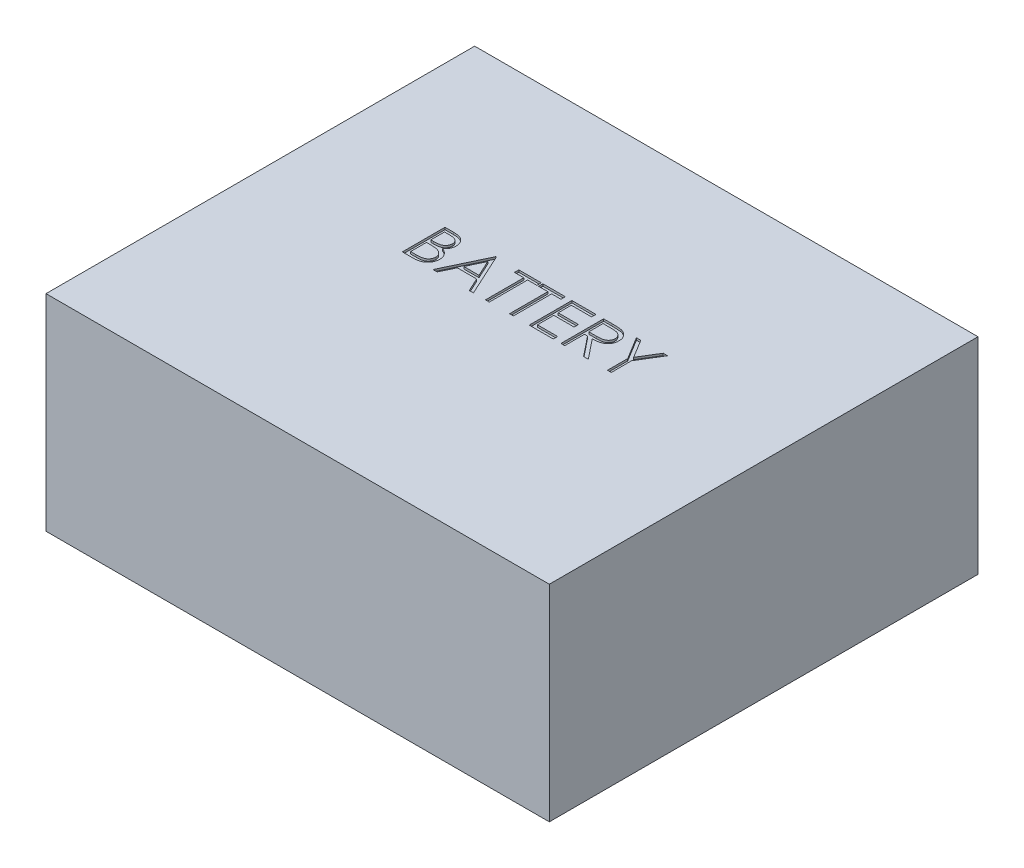
SolidWorks part; units mm, degrees
ref_plane "Front Plane" through (0, 0, 0) normal (0, 0, 1) x (1, 0, 0)
ref_plane "Top Plane" through (0, 0, 0) normal (0, 1, 0) x (1, 0, 0)
ref_plane "Right Plane" through (0, 0, 0) normal (1, 0, 0) x (0, 0, -1)
sketch "Sketch1" plane through (0, 0, 0) normal (0, 1, 0) x (1, 0, 0)
  line L1 (0, 0) -> (236, 0)
  line L2 (0, 0) -> (0, 201)
  line L3 (0, 201) -> (236, 201)
  line L4 (236, 0) -> (236, 201)
  dimension "D1" = 201
  dimension "D2" = 236
extrude "Boss-Extrude1" add sketch "Sketch1" along normal blind 96.5
sketch "Sketch2" plane through (0, 96.5, 0) normal (0, 1, 0) x (1, 0, 0)
  line L0 (0, 100.5) -> (236, 100.5) construction
  line L1 (0, 201) -> (0, 0) construction
  line L2 (236, 0) -> (236, 201) construction
  text T0 "BATTERY" font "Century Gothic" height 20
extrude "Cut-Extrude1" cut sketch "Sketch2" against normal blind 1
